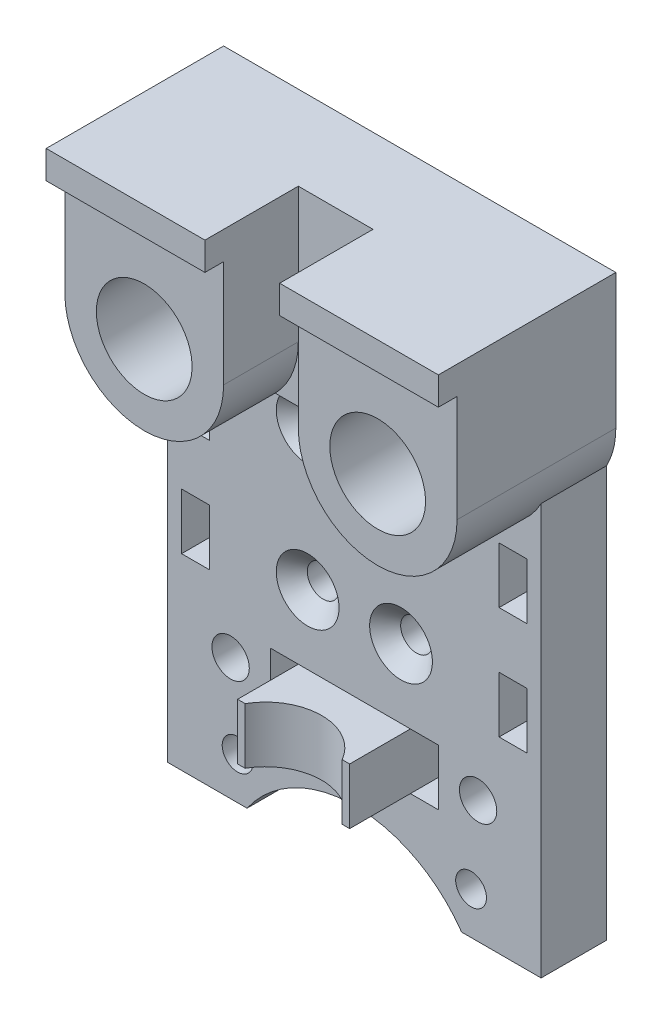
SolidWorks part; units mm, degrees
material "PA Type 6"
ref_plane "Front Plane" through (0, 0, 0) normal (0, 0, 1) x (1, 0, 0)
ref_plane "Top Plane" through (0, 0, 0) normal (0, 1, 0) x (1, 0, 0)
ref_plane "Right Plane" through (0, 0, 0) normal (1, 0, 0) x (0, 0, -1)
sketch "Sketch1" plane through (0, 0, 0) normal (0, 0, 1) x (1, 0, 0)
  line L0 (-15, -2) -> (-20, -7)
  line L1 (-15, -42) -> (15, -42)
  line L2 (-15, -42) -> (-15, 0)
  line L3 (-15, 0) -> (15, 0)
  line L4 (15, -42) -> (15, 0)
  line L5 (0, 0) -> (0, -42) construction
  line L6 (-15, -21) -> (15, -21) construction
  line L7 (-20, -7) -> (-20, -42)
  line L8 (-20, -42) -> (-15, -42)
  line L9 (15, -2) -> (20, -7)
  line L10 (20, -7) -> (20, -42)
  line L11 (20, -42) -> (15, -42)
  point P224 (0, -21)
  dimension "D1" = 30
  dimension "D2" = 42
  dimension "D3" = 40
  dimension "D4" = 35
  dimension "D5" = 45
extrude "Boss-Extrude1" add sketch "Sketch1" against normal blind 7 contours L1 L4 L3 L2 | L7 L8 L2 L0 | L11 L10 L9 L4 region at (-17.4444, -23.2222, 0) region at (0, -21, 0) region at (17.4444, -23.2222, 0)
hole_wizard "CSK for M3 SFHCS1" positions "Sketch2" profile "Sketch3" countersink size "M3" standard "ANSI Metric" end condition through all
sketch "Sketch2" plane through (0, 0, 0) normal (0, 0, 1) x (1, 0, 0)
  line L1 (-5, -3.5) -> (5, -3.5)
  line L2 (-5, -3.5) -> (-5, -18.5)
  line L3 (-5, -18.5) -> (5, -18.5)
  line L4 (5, -3.5) -> (5, -18.5)
  line L5 (0, -3.5) -> (0, 0) construction
  line L7 (-5, -11) -> (5, -11) construction
  point P0 (-5, -3.5)
  point P2 (5, -3.5)
  point P4 (-5, -18.5)
  point P6 (5, -18.5)
  dimension "D1" = 15
  dimension "D2" = 10
  dimension "D3" = 11
sketch "Sketch3" plane through (-5, -3.5, 0) normal (1, 0, 0) x (0, -1, 0)
  line L0 (0, 0) -> (0, 7)
  line L1 (0, 7) -> (1.7, 7)
  line L2 (1.7, 7) -> (1.7, 1.66)
  line L3 (1.7, 1.66) -> (3.36, 0)
  line L5 (3.36, 0) -> (0, 0)
  line L6 (-1.7, 1.66) -> (-3.36, 0) construction
  line L11 (0, -6.35) -> (0, 107.95) construction
  dimension "Thru Hole Dia." = 3.4
  dimension "Thru Hole Depth" = 7
  dimension "Near C'Sink Dia." = 6.72
  dimension "Near C'Sink Angle" = 90
sketch "Sketch4" plane through (0, 0, 0) normal (0, 0, 1) x (1, 0, 0)
  line L0 (0, -50) -> (0, 0) construction
  circle A0 centre (0, -50) radius 14
  dimension "D2" = 28
  dimension "D1" = 50
extrude "Cut-Extrude1" cut sketch "Sketch4" against normal blind 10
hole_wizard "M4x0.7 Tapped Hole1" positions "Sketch6" profile "Sketch7" tap size "M4x0.7" standard "ANSI Metric" end condition through all
sketch "Sketch6" plane through (0, 0, 0) normal (0, 0, 1) x (1, 0, 0)
  line L0 (-12.5, -37.5) -> (12.5, -37.5) construction
  line L2 (0, -37.5) -> (0, 0) construction
  arc A0 (11.4891, -42) -> (-11.4891, -42) centre (0, -50) ccw construction
  point P2 (-12.5, -37.5)
  point P4 (12.5, -37.5)
  dimension "D1" = 12.5
  dimension "D2" = 25
sketch "Sketch7" plane through (-12.5, -37.5, 0) normal (1, 0, 0) x (0, -1, 0)
  line L0 (0, 0) -> (0, 7)
  line L1 (0, 7) -> (1.65, 7)
  line L2 (1.65, 7) -> (1.65, 0)
  line L5 (1.65, 0) -> (0, 0)
  line L11 (0, -6.35) -> (0, 107.95) construction
  dimension "Thru Tap Drill Dia." = 3.3
  dimension "Thru Tap Drill Depth" = 7
cosmetic thread "Hole Thread1" parameters "D2"=4
cosmetic thread "Hole Thread2" parameters "D2"=4
sketch "Sketch8" plane through (0, 0, 0) normal (0, 0, 1) x (1, 0, 0)
  line L0 (-15, 0) -> (15, 0) construction
  line L1 (-6, -31.9) -> (6, -31.9)
  line L2 (-6, -31.9) -> (-6, -25.9)
  line L3 (-6, -25.9) -> (6, -25.9)
  line L4 (6, -31.9) -> (6, -25.9)
  line L5 (0, -25.9) -> (0, -31.9) construction
  line L6 (-6, -28.9) -> (6, -28.9) construction
  point P0 (0, -28.9)
  dimension "D1" = 6
  dimension "D2" = 25.9
  dimension "D3" = 12
extrude "Boss-Extrude2" add sketch "Sketch8" along normal blind 6.5
sketch "Sketch9" plane through (0, -25.9, 0) normal (0, 1, 0) x (1, 0, 0)
  line L0 (0, -9.5) -> (0, 0) construction
  circle A0 centre (0, -9.5) radius 6
  dimension "D1" = 12
  dimension "D2" = 9.5
extrude "Cut-Extrude2" cut sketch "Sketch9" against normal blind 10
sketch "Sketch13" plane through (0, 0, 0) normal (0, 0, 1) x (1, 0, 0)
  line L1 (-6, -31.9) -> (-9, -31.9)
  line L2 (-6, -31.9) -> (-6, -25.9)
  line L3 (-6, -25.9) -> (-9, -25.9)
  line L4 (-9, -31.9) -> (-9, -25.9)
  line L5 (-7.5, -25.9) -> (-7.5, -31.9) construction
  line L6 (-6, -28.9) -> (-9, -28.9) construction
  line L7 (6, -31.9) -> (9, -31.9)
  line L8 (6, -31.9) -> (6, -25.9)
  line L9 (6, -25.9) -> (9, -25.9)
  line L10 (9, -31.9) -> (9, -25.9)
  line L11 (7.5, -25.9) -> (7.5, -31.9) construction
  line L12 (6, -28.9) -> (9, -28.9) construction
  point P92 (-7.5, -28.9)
  point P122 (7.5, -28.9)
  dimension "D1" = 3
extrude "Cut-Extrude4" cut sketch "Sketch13" against normal blind 10
sketch "Sketch10" plane through (0, 0, 0) normal (0, 0, 1) x (1, 0, 0)
  line L1 (-15, 0) -> (15, 0)
  line L2 (-15, 0) -> (-15, 5.35)
  line L3 (-15, 5.35) -> (15, 5.35)
  line L4 (15, 0) -> (15, 5.35)
  line L5 (0, 5.35) -> (0, 0) construction
  line L6 (-15, 2.675) -> (15, 2.675) construction
  point P196 (0, 2.675)
  dimension "D1" = 5.35
extrude "Boss-Extrude3" [suppressed] add sketch "Sketch10" against normal up to surface and the other way blind 8 up to face at (-7.5, -28.9, -7)
sketch "Sketch12" [suppressed] plane through (0, 5.35, 0) normal (0, 1, 0) x (1, 0, 0)
  line L0 (-11, -4) -> (-15, -4) construction
  line L1 (-4, -4.25) -> (-15, -4.25) construction
  line L2 (-15, -8) -> (-15, 5) construction
  line L3 (-9.0112, -2.2111) -> (-8.4888, 2.7111) construction
  line L4 (-2, -2.25) -> (-2, 2.5) construction
  line L5 (0, 0) -> (0, 2.5) construction
  line L6 (0, 5) -> (0, -8) construction
  line L7 (-15, 5) -> (15, 5) construction
  line L8 (15, -8) -> (-15, -8) construction
  line L9 (0, 2.5) -> (-6.5, 2.5) construction
  circle A0 centre (-11, -2) radius 2
  circle A1 centre (-4, -2.25) radius 2
  circle A2 centre (-6.5, 2.5) radius 1.75
  circle A3 centre (0, 2.5) radius 1.75
  circle A4 centre (-6.5, 2.5) radius 2 construction
  circle A5 centre (0, 2.5) radius 2 construction
  circle A6 centre (11, -2) radius 2
  circle A7 centre (4, -2.25) radius 2
  circle A8 centre (6.5, 2.5) radius 1.75
  dimension "D1" = 4
  dimension "D4" = 3.5
  dimension "D9" = 4
  dimension "D2" = 4
  dimension "D3" = 0.25
  dimension "D5" = 4
  dimension "D6" = 11
  dimension "D7" = 2.5
  dimension "D8" = 6.5
extrude "Cut-Extrude3" [suppressed] cut sketch "Sketch12" against normal blind 6
sketch "Sketch14" plane through (0, 0, 0) normal (0, 0, 1) x (1, 0, 0)
  line L1 (-24, 0) -> (24, 0)
  line L2 (-24, 0) -> (-24, 17)
  line L3 (-24, 17) -> (24, 17)
  line L4 (24, 0) -> (24, 17)
  line L5 (0, 17) -> (0, 0) construction
  line L6 (-24, 8.5) -> (24, 8.5) construction
  point P120 (0, 8.5)
  dimension "D1" = 17
  dimension "D2" = 48
extrude "Boss-Extrude5" add sketch "Sketch14" against normal up to surface (7 mm away) and the other way blind 10 up to face at (-7.5, -28.9, -7)
sketch "Sketch15" plane through (0, 0, -7) normal (0, 0, -1) x (-1, 0, 0)
  line L0 (-12.5, 6) -> (12.5, 6) construction
  line L3 (0, 6) -> (0, 0) construction
  circle A6 centre (12.5, 6) radius 5.125
  circle A7 centre (-12.5, 6) radius 5.125
  dimension "D2" = 25
  dimension "D3" = 10.25
  dimension "D1" = 6
extrude "Cut-Extrude5" cut sketch "Sketch15" against normal through all
sketch "Sketch16" plane through (0, 0, 10) normal (0, 0, 1) x (1, 0, 0)
  circle A0 centre (-12.5, 6) radius 8.5
  circle A1 centre (12.5, 6) radius 8.5
  circle A2 centre (12.5, 6) radius 5.125 construction
  circle A3 centre (-12.5, 6) radius 5.125 construction
  circle A4 centre (12.5, 6) radius 5.125
  circle A5 centre (-12.5, 6) radius 5.125
  dimension "D1" = 17
extrude "Boss-Extrude6" add sketch "Sketch16" against normal up to surface (17 mm away) up to face at (-17.625, 6, -7)
sketch "Sketch18" plane through (0, 0, -7) normal (0, 0, -1) x (-1, 0, 0)
  line L0 (0, 5.25) -> (0, 0) construction
  circle A0 centre (0, 5.25) radius 1.75
  circle A1 centre (0, 5.25) radius 5.75
  dimension "D1" = 3.5
  dimension "D2" = 3.5
  dimension "D3" = 4
extrude "Boss-Extrude7" add sketch "Sketch18" along normal blind 6.5 separate body
sketch "Sketch19" plane through (0, 0, -7) normal (0, 0, -1) x (-1, 0, 0)
  circle A0 centre (0, 5.25) radius 1.75 construction
  circle A1 centre (0, 5.25) radius 1.75
extrude "Cut-Extrude6" cut sketch "Sketch19" against normal up to surface (17 mm away) up to face at (0, 3.625, 10)
sketch "Sketch20" plane through (0, 0, 10) normal (0, 0, 1) x (1, 0, 0)
  line L0 (24, 17) -> (-24, 17) construction
  line L1 (-16, 17) -> (16, 17)
  line L2 (-16, 17) -> (-16, 14)
  line L3 (-16, 14) -> (16, 14)
  line L4 (16, 17) -> (16, 14)
  line L5 (0, 14) -> (0, 17) construction
  line L6 (-16, 15.5) -> (16, 15.5) construction
  line L7 (0, 0) -> (0, 14) construction
  point P232 (0, 15.5)
  dimension "D1" = 3
  dimension "D2" = 32
extrude "Boss-Extrude8" add sketch "Sketch20" along normal blind 3
sketch "Sketch22" plane through (0, 0, 10) normal (0, 0, 1) x (1, 0, 0)
  line L0 (-6.4792, 0) -> (6.4792, 0) construction
  line L1 (-4, 0) -> (4, 0)
  line L2 (-4, 0) -> (-4, 17)
  line L3 (-4, 17) -> (4, 17)
  line L4 (4, 0) -> (4, 17)
  line L5 (0, 17) -> (0, 0) construction
  line L6 (-4, 8.5) -> (4, 8.5) construction
  line L7 (16, 17) -> (-16, 17) construction
  line L8 (6.4792, 0) -> (4, 0)
  line L9 (-4, 0) -> (-6.4792, 0)
  arc A0 (-6.4792, 0) -> (-4, 6) centre (-12.5, 6) ccw
  arc A4 (6.4792, 0) -> (4, 6) centre (12.5, 6) cw
  circle A5 centre (12.5, 6) radius 5.125 construction
  circle A6 centre (-12.5, 6) radius 5.125 construction
  point P300 (0, 8.5)
  circle M4 centre (0, 5.25) radius 1.75
  line M10 (-6.4792, 0) -> (6.4792, 0)
  line M16 (16, 14) -> (-16, 14)
  dimension "D1" = 8
extrude "Cut-Extrude7" cut sketch "Sketch22" against normal blind 8 and the other way blind 8 contours L4 L2 M10 M16 M4 | A0 L2 M10 | A4 L4 M10 | L4 L3 L2 M16 region at (0, 7.1645, 10) region at (-4.7206, 1.4527, 10) region at (4.7206, 1.4527, 10) region at (0, 15.5, 10)
hole_wizard "Ø4.0 (4) Diameter Hole1" positions "Sketch23" profile "Sketch24" hole size "Ø4.0" standard "ANSI Metric" end condition up to next
sketch "Sketch23" plane through (0, 0, -7) normal (0, 0, -1) x (-1, 0, 0)
  line L0 (-13.25, -28.9) -> (13.25, -28.9) construction
  line L3 (0, -28.9) -> (0, 0) construction
  line L4 (6, -25.9) -> (6, -31.9) construction
  point P0 (-13.25, -28.9)
  point P2 (13.25, -28.9)
  point P14 (6, -28.9)
  dimension "D1" = 26.5
sketch "Sketch24" plane through (13.25, -28.9, -7) normal (1, 0, 0) x (0, 1, 0)
  line L0 (0, 0) -> (0, 7.001)
  line L1 (0, 7.001) -> (2, 7.001)
  line L2 (2, 7.001) -> (2, 0)
  line L5 (2, 0) -> (0, 0)
  line L11 (0, -6.35) -> (0, 107.95) construction
  dimension "Thru Hole Dia." = 4
  dimension "Thru Hole Depth" = 7.001
sketch "Sketch25" plane through (0, 0, 10) normal (0, 0, 1) x (1, 0, 0)
  line L0 (-12.5, 6) -> (-12.5, 17) construction
  line L1 (-4, 17) -> (-16, 17) construction
  line L2 (-21, 6) -> (-21, 17)
  line L3 (-4, 6) -> (-4, 17)
  line L4 (12.5, 6) -> (12.5, 17) construction
  line L5 (-24, 17) -> (-18.5208, 17)
  line L6 (-24, 17) -> (-24, 0)
  line L7 (-24, 0) -> (-18.5208, 0)
  line L8 (-18.5208, 17) -> (-18.5208, 0)
  line L9 (-21.2604, 0) -> (-21.2604, 17) construction
  line L10 (-24, 8.5) -> (-18.5208, 8.5) construction
  line L11 (16, 17) -> (4, 17) construction
  line L12 (4, 6) -> (4, 17)
  line L13 (21, 6) -> (21, 17)
  line L14 (24, 17) -> (16, 17) construction
  line L15 (18.5208, 0) -> (24, 0)
  line L16 (18.5208, 0) -> (18.5208, 17)
  line L17 (18.5208, 17) -> (24, 17)
  line L18 (24, 0) -> (24, 17)
  line L19 (21.2604, 17) -> (21.2604, 0) construction
  line L20 (18.5208, 8.5) -> (24, 8.5) construction
  arc A0 (-21, 6) -> (-4, 6) centre (-12.5, 6) ccw
  arc A1 (-4, 17) -> (-21, 17) centre (-12.5, 17) ccw
  arc A2 (4, 6) -> (21, 6) centre (12.5, 6) ccw
  arc A3 (21, 17) -> (4, 17) centre (12.5, 17) ccw
  point P5 (-12.5, 11.5)
  point P19 (12.5, 11.5)
  point P119 (-21.2604, 8.5)
  point P223 (21.2604, 8.5)
  line M3 (18.5208, 0) -> (24, 0)
  line M4 (24, 0) -> (24, 17)
  line M5 (24, 17) -> (16, 17)
extrude "Cut-Extrude8" cut sketch "Sketch25" against normal up to next contours A0 L2 L5 L6 L7 | A2 L13 M3 M4 M5 region at (-22.3153, 7.9137, 10) region at (22.3153, 7.9137, 10)
other "Move Face2" face at (0, 17, 6.8333) offset 0.43 parameters "D1"=0.43
sketch "Sketch26" plane through (0, 0, 13) normal (0, 0, 1) x (1, 0, 0)
  line L1 (-16, 14) -> (16, 14)
  line L2 (-16, 14) -> (-16, 17.43)
  line L3 (-16, 17.43) -> (16, 17.43)
  line L4 (16, 14) -> (16, 17.43)
  line L5 (0, 17.43) -> (0, 14) construction
  line L6 (-16, 15.715) -> (16, 15.715) construction
  point P148 (0, 15.715)
extrude "Cut-Extrude9" cut sketch "Sketch26" against normal up to surface (3 mm away) up to face at (-17.625, 6, 10)
sketch "Sketch27" plane through (0, 17.43, 0) normal (0, 1, 0) x (1, 0, 0)
  line L1 (-21, -10) -> (-4, -10) construction
  line L2 (-21, -10) -> (-21, -12)
  line L3 (-21, -12) -> (-4, -12)
  line L4 (-4, -10) -> (-4, -12)
  line L5 (-12.5, -12) -> (-12.5, -10) construction
  line L6 (-21, -11) -> (-4, -11) construction
  line L7 (4, -10) -> (21, -10) construction
  line L8 (-21, -10) -> (-4, -10)
  line L9 (-4, -10) -> (-4, -2)
  line L10 (-4, -2) -> (4, -2)
  line L11 (4, -2) -> (4, -10)
  line L12 (4, -10) -> (21, -10)
  line L13 (21, -10) -> (21, 7)
  line L14 (21, 7) -> (-21, 7)
  line L15 (-21, 7) -> (-21, -10)
  line L16 (-21, -10) -> (-4, -10) construction
  line L17 (-4, -10) -> (-4, -2)
  line L18 (-4, -2) -> (4, -2)
  line L19 (4, -2) -> (4, -10)
  line L20 (4, -10) -> (21, -10) construction
  line L21 (21, -10) -> (21, 7)
  line L22 (21, 7) -> (-21, 7)
  line L23 (-21, 7) -> (-21, -10)
  line L24 (4, -10) -> (4, -12)
  line L25 (4, -12) -> (21, -12)
  line L26 (21, -10) -> (21, -12)
  line L27 (12.5, -12) -> (12.5, -10) construction
  line L28 (4, -11) -> (21, -11) construction
  point P145 (12.5, -11)
  point P246 (-12.5, -11)
  dimension "D2" = 2
  dimension "D1" = 0
extrude "Boss-Extrude9" add sketch "Sketch27" along normal blind 3
other "DeleteFace1" face at (-17.5472, -4.5472, -3.5) face at (17.5472, -4.5472, -3.5) and patch yes
sketch "Sketch28" plane through (0, 0, 0) normal (0, 0, 1) x (1, 0, 0)
  line L0 (20, 2) -> (20, -42) construction
  line L1 (18.5, -15.9) -> (15.5, -15.9)
  line L2 (18.5, -15.9) -> (18.5, -21.9)
  line L3 (18.5, -21.9) -> (15.5, -21.9)
  line L4 (15.5, -15.9) -> (15.5, -21.9)
  line L5 (17, -21.9) -> (17, -15.9) construction
  line L6 (18.5, -18.9) -> (15.5, -18.9) construction
  line L7 (18.5, -3.9) -> (15.5, -3.9)
  line L8 (18.5, -3.9) -> (18.5, -9.9)
  line L9 (18.5, -9.9) -> (15.5, -9.9)
  line L10 (15.5, -3.9) -> (15.5, -9.9)
  line L11 (17, -9.9) -> (17, -3.9) construction
  line L12 (18.5, -6.9) -> (15.5, -6.9) construction
  line L13 (9, -25.9) -> (6, -25.9) construction
  line L16 (0, 0) -> (0, -36) construction
  line L17 (-18.5, -6.9) -> (-15.5, -6.9) construction
  line L18 (-17, -9.9) -> (-17, -3.9) construction
  line L19 (-18.5, -18.9) -> (-15.5, -18.9) construction
  line L20 (-17, -21.9) -> (-17, -15.9) construction
  line L21 (-15.5, -3.9) -> (-15.5, -9.9)
  line L22 (-18.5, -9.9) -> (-15.5, -9.9)
  line L23 (-18.5, -3.9) -> (-18.5, -9.9)
  line L24 (-18.5, -3.9) -> (-15.5, -3.9)
  line L25 (-15.5, -15.9) -> (-15.5, -21.9)
  line L26 (-18.5, -21.9) -> (-15.5, -21.9)
  line L27 (-18.5, -15.9) -> (-18.5, -21.9)
  line L28 (-18.5, -15.9) -> (-15.5, -15.9)
  arc A0 (11.4891, -42) -> (-11.4891, -42) centre (0, -50) ccw construction
  point P33 (-17, -18.9)
  point P34 (-17, -6.9)
  point P112 (17, -6.9)
  point P184 (17, -18.9)
  dimension "D1" = 6
  dimension "D2" = 3
  dimension "D3" = 1.5
  dimension "D4" = 4
  dimension "D5" = 6
extrude "Cut-Extrude10" cut sketch "Sketch28" against normal through all
